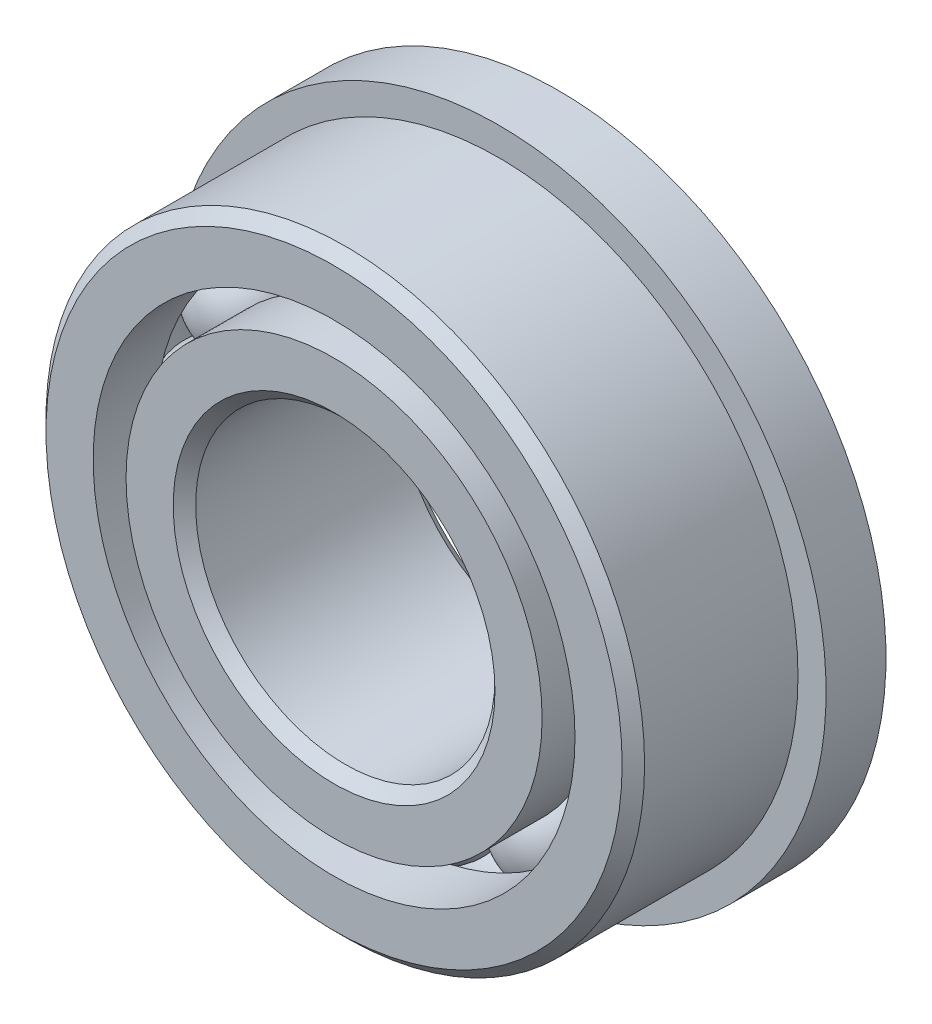
SolidWorks part; units mm, degrees
material "Cast Alloy Steel"
ref_plane "Front Plane" through (0, 0, 0) normal (0, 0, 1) x (1, 0, 0)
ref_plane "Top Plane" through (0, 0, 0) normal (0, 1, 0) x (1, 0, 0)
ref_plane "Right Plane" through (0, 0, 0) normal (1, 0, 0) x (0, 0, -1)
sketch "Sketch1" plane through (0, 0, 0) normal (1, 0, 0) x (0, 0, -1)
  line L0 (-2.3813, 0) -> (2.3813, 0) construction
  line L1 (0, 6.35) -> (0, -6.35) construction
  line L2 (2.1431, 6.35) -> (-2.1431, 6.35)
  line L3 (-2.1431, 6.35) -> (-2.3813, 6.1119)
  line L4 (-2.3813, 6.1119) -> (-2.3813, 5.1114)
  line L5 (-2.3813, 5.1114) -> (-1.0583, 5.1114)
  line L6 (2.3813, 5.1114) -> (1.0583, 5.1114)
  line L7 (2.3813, 6.1119) -> (2.3813, 5.1114)
  line L8 (2.1431, 6.35) -> (2.3813, 6.1119)
  line L9 (0, 6.35) -> (0, 4.7625) construction
  line L10 (0, 4.7625) -> (0, 3.175) construction
  arc A0 (-1.0583, 5.1114) -> (1.0583, 5.1114) centre (0, 4.7625) cw
  point P14 (0, 3.175)
  dimension "OD" = 12.7
  dimension "D1" = 45
  dimension "D2" = 0.2381
  dimension "Shaft Dia" = 6.35
  dimension "D3" = 2.1167
  dimension "D4" = 0.3489
  dimension "Width" = 4.7625
revolve "Revolve1" add sketch "Sketch1" angle 360 about L0
sketch "Sketch3" plane through (0, 0, 0) normal (1, 0, 0) x (0, 0, -1)
  line L0 (-2.1431, 6.35) -> (-2.3813, 6.1119) construction
  line L1 (-1.0583, 4.4136) -> (-2.3813, 4.4136)
  line L2 (-2.3813, 6.1119) -> (-2.3813, 5.1114) construction
  line L3 (-2.3813, 4.4136) -> (-2.3813, 3.4131)
  line L5 (-2.3813, 3.4131) -> (-2.1431, 3.175)
  line L6 (-2.1431, 3.175) -> (2.1431, 3.175)
  line L7 (2.3813, 6.1119) -> (2.3813, 5.1114) construction
  line L8 (2.1431, 3.175) -> (2.3813, 3.4131)
  line L10 (2.3813, 3.4131) -> (2.3813, 4.4136)
  line L11 (2.3813, 4.4136) -> (1.0583, 4.4136)
  line L13 (2.1431, 6.35) -> (2.3813, 6.1119) construction
  arc A1 (1.0583, 4.4136) -> (-1.0583, 4.4136) centre (0, 4.7625) cw
  arc A2 (1.0583, 5.1114) -> (-1.0583, 5.1114) centre (0, 4.7625) ccw construction
revolve "Revolve3" add sketch "Sketch3" angle 360 about L0
sketch "Sketch5" plane through (0, 0, 0) normal (1, 0, 0) x (0, 0, -1)
  line L0 (2.3813, 6.1119) -> (2.3813, 5.1114) construction
  line L1 (2.3813, 5.6116) -> (1.1113, 5.6116)
  line L2 (2.3813, 5.6116) -> (2.3813, 6.9469)
  line L3 (2.3813, 6.9469) -> (1.1113, 6.9469)
  line L4 (1.1113, 5.6116) -> (1.1113, 6.9469)
  line L5 (2.3813, 0) -> (-2.3813, 0) construction
  dimension "Th" = 1.27
  dimension "Flange OD" = 13.8938
revolve "Revolve5" add sketch "Sketch5" angle 360 about L5
sketch "Sketch4" plane through (0, 0, 0) normal (1, 0, 0) x (0, 0, -1)
  line L0 (-1.1144, 4.7625) -> (1.1144, 4.7625)
  arc A2 (-1.1144, 4.7625) -> (1.1144, 4.7625) centre (0, 4.7625) cw
  arc A3 (1.0583, 5.1114) -> (-1.0583, 5.1114) centre (0, 4.7625) ccw construction
revolve "Revolve4" add sketch "Sketch4" angle 360 about L0
ref_axis "Axis1" through (0, 0, -2.3813) along (0, 0, 1)
pattern_circular "CirPattern1" count 12 every 30 about axis through (0, 0, -2.3813) along (0, 0, 1) of bodies 104
equation "\"D2@Sketch1\" = \"Width@Sketch1\"*.05"
equation "\"D3@Sketch1\" = \"Width@Sketch1\"/2.25"
equation "\"D4@Sketch1\" = (((\"OD@Sketch1\"-\"Width@Sketch1\")/2)/3.25)/3.5"
equation "\"D2@CirPattern1\" = 360/\"Balls@CirPattern1\""
